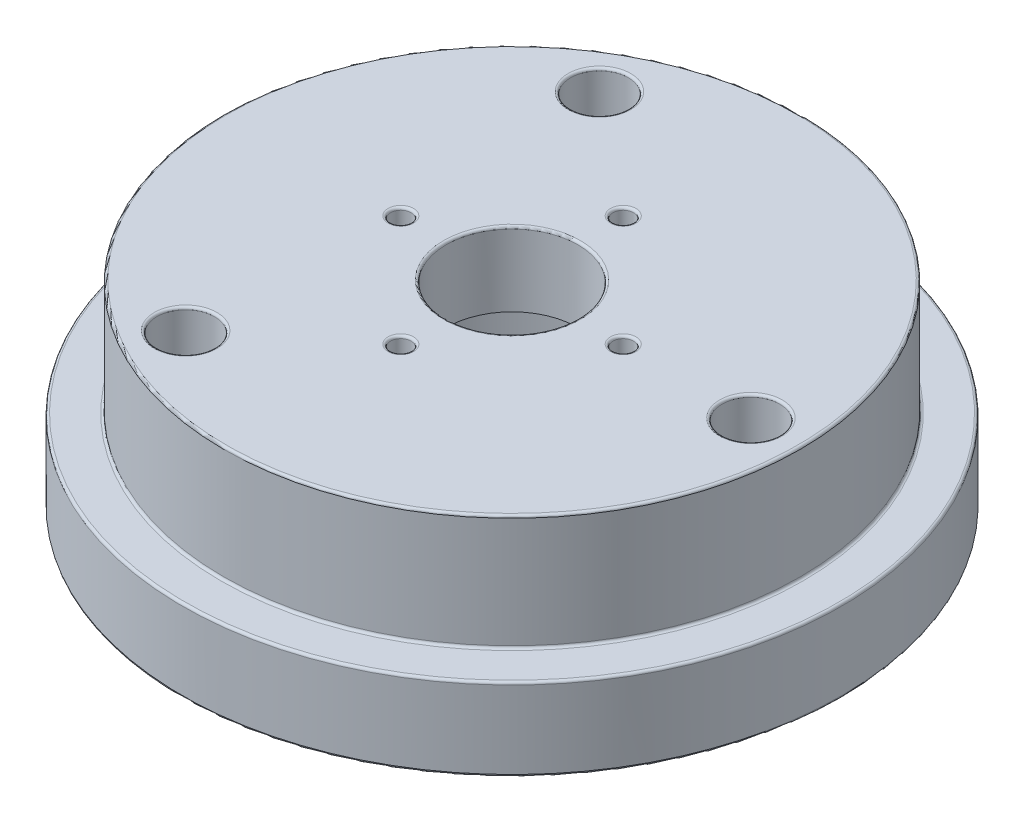
SolidWorks part; units mm, degrees
material "AISI 1020"
ref_plane "Front Plane" through (0, 0, 0) normal (0, 0, 1) x (1, 0, 0)
ref_plane "Top Plane" through (0, 0, 0) normal (0, 1, 0) x (1, 0, 0)
ref_plane "Right Plane" through (0, 0, 0) normal (1, 0, 0) x (0, 0, -1)
sketch "Sketch1" plane through (0, 0, 0) normal (0, 0, 1) x (1, 0, 0)
  line L0 (0, 0) -> (-20, 0)
  line L1 (-20, 0) -> (-20, 5)
  line L2 (-20, 5) -> (-17.5, 5)
  line L3 (-17.5, 5) -> (-17.5, 12)
  line L4 (-17.5, 12) -> (0, 12)
  line L5 (0, 12) -> (0, 0)
  dimension "D1" = 17.5
  dimension "D2" = 12
  dimension "D3" = 5
  dimension "D4" = 20
revolve "Revolve1" add sketch "Sketch1" angle 360 about L5
sketch "Sketch2" plane through (0, 0, 0) normal (0, -1, 0) x (1, 0, 0)
  circle A0 centre (0, 0) radius 10
  circle A1 centre (14.5, 0) radius 1.75
  circle A2 centre (0, 0) radius 10
  circle A3 centre (-7.25, -12.5574) radius 1.75
  circle A4 centre (0, 0) radius 10
  circle A5 centre (-7.25, 12.5574) radius 1.75
  circle A6 centre (0, 0) radius 4
  circle A7 centre (6.75, 0) radius 0.625
  circle A8 centre (0, -6.75) radius 0.625
  circle A9 centre (-6.75, 0) radius 0.625
  circle A10 centre (0, 6.75) radius 0.625
  dimension "D1" = 20
  dimension "D2" = 3.5
  dimension "D5" = 8
  dimension "D6" = 1.25
  dimension "D3" = 14.5
  dimension "D4" = 3
  dimension "D7" = 6.75
  dimension "D8" = 4
extrude "Cut-Extrude1" cut sketch "Sketch2" against normal through all contours A5 | A6 | A10 | A7 | A8 | A9 | A3 | A1 region at (14.5, 0, 0) region at (-7.25, 0, -12.5574) region at (-7.25, 0, 12.5574) region at (0, 0, 0) region at (6.75, 0, 0) region at (0, 0, -6.75) region at (-6.75, 0, 0) region at (0, 0, 6.75)
extrude "Cut-Extrude2" cut sketch "Sketch2<3>" against normal blind 7.5 contours A0 A10 A9 A8 A7 A6 region at (-9.7172, 0, 0)
sketch "Sketch2<3>" plane through (0, 0, 0) normal (0, -1, 0) x (1, 0, 0) same geometry as "Sketch2"
fillet "Fillet1" radius 0.15 16 edges at (-20, 0, 0) (-5.5, 0, -12.5574) (16.25, 0, 0) (-5.5, 0, 12.5574) (10, 0, 0) (-17.5, 5, 0) (-20, 5, 0) (-17.5, 12, 0) (0.625, 12, -6.75) (7.375, 12, 0) (0.625, 12, 6.75) (4, 12, 0) (-6.125, 12, 0) (-5.5, 12, -12.5574) (16.25, 12, 0) (-5.5, 12, 12.5574)
